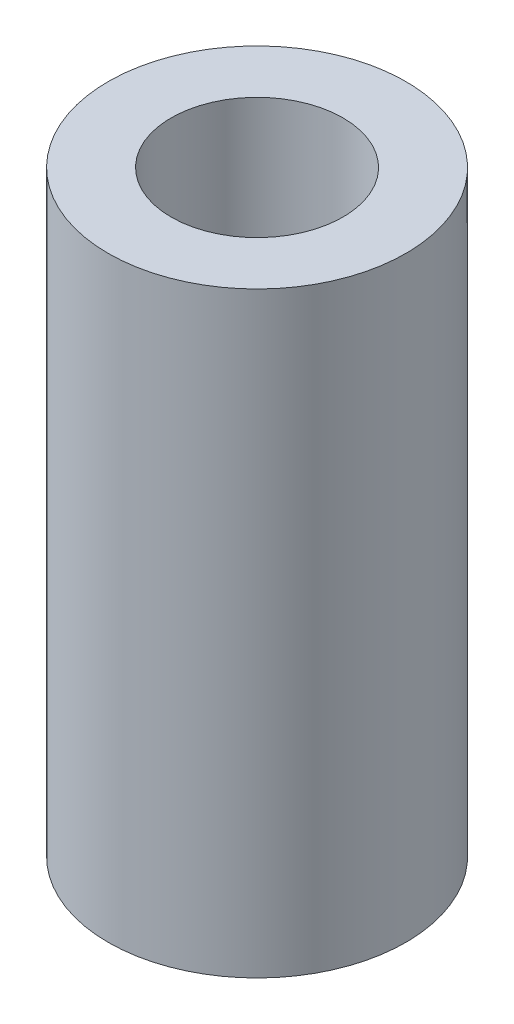
SolidWorks part; units mm, degrees
ref_plane "Front Plane" through (0, 0, 0) normal (0, 0, 1) x (1, 0, 0)
ref_plane "Top Plane" through (0, 0, 0) normal (0, 1, 0) x (1, 0, 0)
ref_plane "Right Plane" through (0, 0, 0) normal (1, 0, 0) x (0, 0, -1)
sketch "Sketch1" plane through (0, 0, 0) normal (0, 1, 0) x (1, 0, 0)
  circle A0 centre (0, 0) radius 7.5
  dimension "SLEEVE_OD" = 15
extrude "Boss-Extrude1" add sketch "Sketch1" along normal blind 30.0653
sketch "Sketch2" plane through (0, 0, 0) normal (0, 1, 0) x (1, 0, 0)
  circle A0 centre (0, 0) radius 4.3306
  dimension "BORE_D" = 8.6611
extrude "Cut-Extrude1" cut sketch "Sketch2" along normal through all
chamfer "Chamfer1" distance 0.9079 angle 68.829 rebuild error yes
